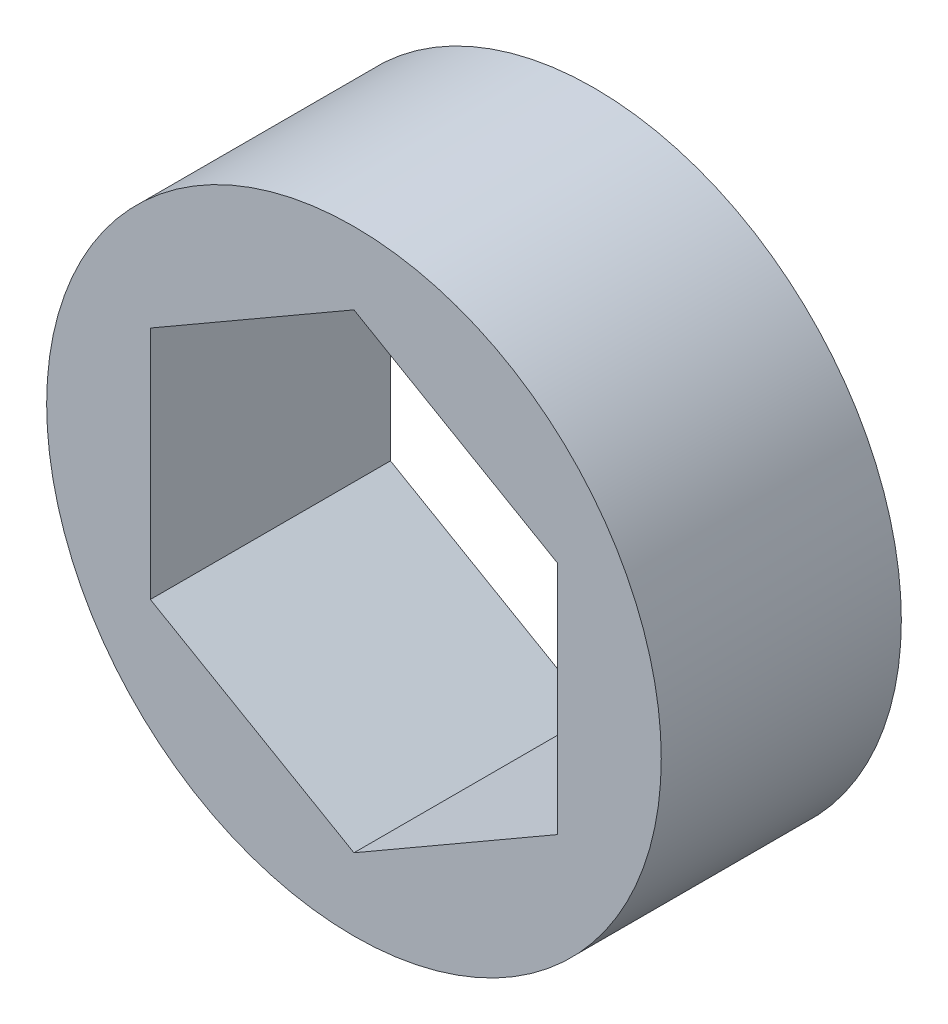
SolidWorks part; units mm, degrees
material "Nylon 101"
ref_plane "Front Plane" through (0, 0, 0) normal (0, 0, 1) x (1, 0, 0)
ref_plane "Top Plane" through (0, 0, 0) normal (0, 1, 0) x (1, 0, 0)
ref_plane "Right Plane" through (0, 0, 0) normal (1, 0, 0) x (0, 0, -1)
sketch "Sketch1" plane through (0, 0, 0) normal (0, 0, 1) x (1, 0, 0)
  line L1 (0, 7.7723) -> (-6.731, 3.8861)
  line L2 (-6.731, 3.8861) -> (-6.731, -3.8861)
  line L3 (-6.731, -3.8861) -> (0, -7.7723)
  line L4 (0, -7.7723) -> (6.731, -3.8861)
  line L5 (6.731, -3.8861) -> (6.731, 3.8861)
  line L6 (6.731, 3.8861) -> (0, 7.7723)
  circle A0 centre (0, 0) radius 10.16
  circle A1 centre (0, 0) radius 6.731 construction
  dimension "D1" = 13.462
  dimension "D2" = 20.32
extrude "Boss-Extrude1" add sketch "Sketch1" along normal mid plane 7.9375
